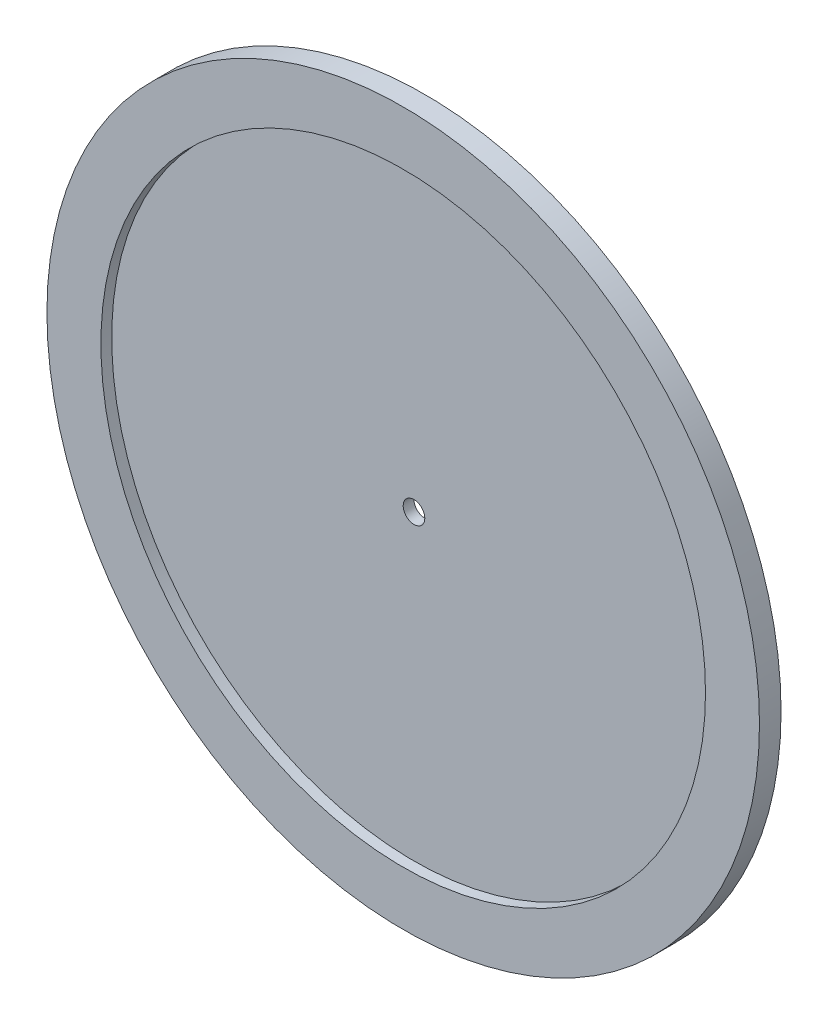
SolidWorks part; units mm, degrees
material "Brass"
ref_plane "Front Plane" through (0, 0, 0) normal (0, 0, 1) x (1, 0, 0)
ref_plane "Top Plane" through (0, 0, 0) normal (0, 1, 0) x (1, 0, 0)
ref_plane "Right Plane" through (0, 0, 0) normal (1, 0, 0) x (0, 0, -1)
sketch "Sketch1" plane through (0, 0, 0) normal (0, 0, 1) x (1, 0, 0)
  line L0 (68.3024, 39.4344) -> (43369.5726, 25039.4344) construction
  line L1 (-57.2402, 33.0476) -> (-43358.5104, 25033.0476) construction
  line L2 (-1000, 0) -> (49000, 0) construction
  line L3 (0, -1000) -> (0, 49000) construction
  line L4 (0, 0) -> (-28678.8218, 40957.6022) construction
  line L5 (0, 0) -> (28678.8218, 40957.6022) construction
  line L6 (-131.9823, 76.2) -> (-32.9956, 19.05) construction
  circle A0 centre (0, 0) radius 104.775
  dimension "dial outer diameter" = 209.55
extrude "Radius" add sketch "Sketch1" along normal blind 6.35
sketch "Sketch3" plane through (0, 0, 6.35) normal (0, 0, 1) x (1, 0, 0)
  line L0 (0, 0) -> (-25000, 43301.2702) construction
  line L1 (0, 0) -> (25000, 43301.2702) construction
  circle A0 centre (0, 0) radius 3.175
  dimension "D2" = 6.35
extrude "Extrude3" cut sketch "Sketch3" against normal through all
sketch "Sketch4" plane through (0, 0, 6.35) normal (0, 0, 1) x (1, 0, 0)
  circle A0 centre (0, 0) radius 88.9
  dimension "dial inner diameter" = 177.8
extrude "Extrude4" cut sketch "Sketch4" against normal blind 3.175
equation "\"D1@Sketch3\" = \"dial outer diameter@Sketch1\"*3/8"
equation "\"dial inner diameter@Sketch4\"=\"dial outer diameter@Sketch1\"*3/4"
